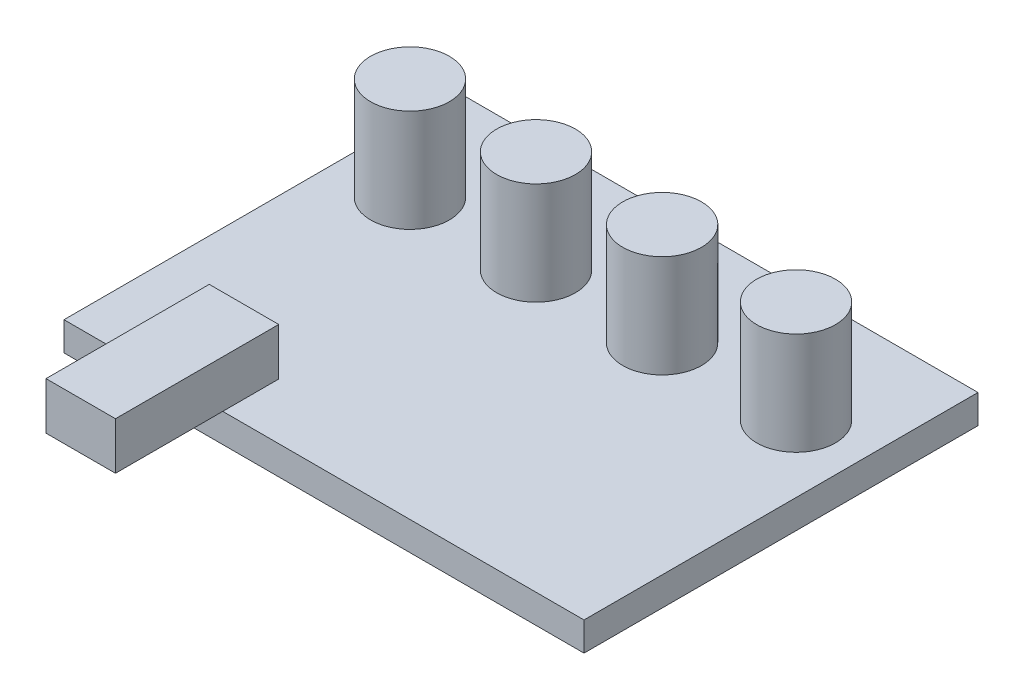
SolidWorks part; units mm, degrees
ref_plane "Front Plane" through (0, 0, 0) normal (0, 0, 1) x (1, 0, 0)
ref_plane "Top Plane" through (0, 0, 0) normal (0, 1, 0) x (1, 0, 0)
ref_plane "Right Plane" through (0, 0, 0) normal (1, 0, 0) x (0, 0, -1)
sketch "Sketch1" plane through (0, 0, 0) normal (0, 1, 0) x (1, 0, 0)
  line L5 (-32.9989, 24.3) -> (32.9989, 24.3)
  line L6 (0, 0) -> (0, 24.3) construction
  line L8 (0, 0) -> (0, -34.8967) construction
  line L25 (32.9989, -25.7) -> (-32.9989, -25.7)
  line L27 (32.9989, 24.3) -> (32.9989, -25.7)
  line L31 (-32.9989, 24.3) -> (-32.9989, -25.7)
  point P4 (0, 0)
  point P5 (0, 0)
  point P7 (0, -25.7)
  dimension "D1" = 25.7
  dimension "D2" = 32.9989
  dimension "D3" = 24.3
extrude "Boss-Extrude1" add sketch "Sketch1" along normal blind 3.65
sketch "Sketch2" plane through (0, 3.65, 0) normal (0, 1, 0) x (1, 0, 0)
  line L0 (-29.5, 9.7116) -> (-34.5, 9.7116) construction
  line L2 (29.5, 9.7116) -> (34.5, 9.7116) construction
  line L3 (34.5, -30.6935) -> (34.5, 29.3065) construction
  line L4 (-24.5, 9.7116) -> (-8.5, 9.7116) construction
  line L5 (-8.5, 9.7116) -> (7.5, 9.7116) construction
  line L6 (7.5, 9.7116) -> (24.5, 9.7116) construction
  line L7 (-34.5, 29.3065) -> (-34.5, -30.6935) construction
  circle A0 centre (-24.5, 9.7116) radius 5
  circle A1 centre (-8.5, 9.7116) radius 5
  circle A2 centre (7.5, 9.7116) radius 5
  circle A3 centre (24.5, 9.7116) radius 5
  dimension "D1" = 10
  dimension "D2" = 5
  dimension "D3" = 5
  dimension "D4" = 17
extrude "Boss-Extrude2" add sketch "Sketch2" along normal blind 13
sketch "Sketch3" plane through (0, 3.65, 0) normal (0, 1, 0) x (1, 0, 0)
  line L1 (-21.666, -18.5966) -> (-12.8497, -18.5966)
  line L2 (-21.666, -18.5966) -> (-21.666, -39.3148)
  line L3 (-21.666, -39.3148) -> (-12.8497, -39.3148)
  line L4 (-12.8497, -18.5966) -> (-12.8497, -39.3148)
  point P4 (-21.666, -39.3148)
extrude "Boss-Extrude3" add sketch "Sketch3" along normal blind 6
